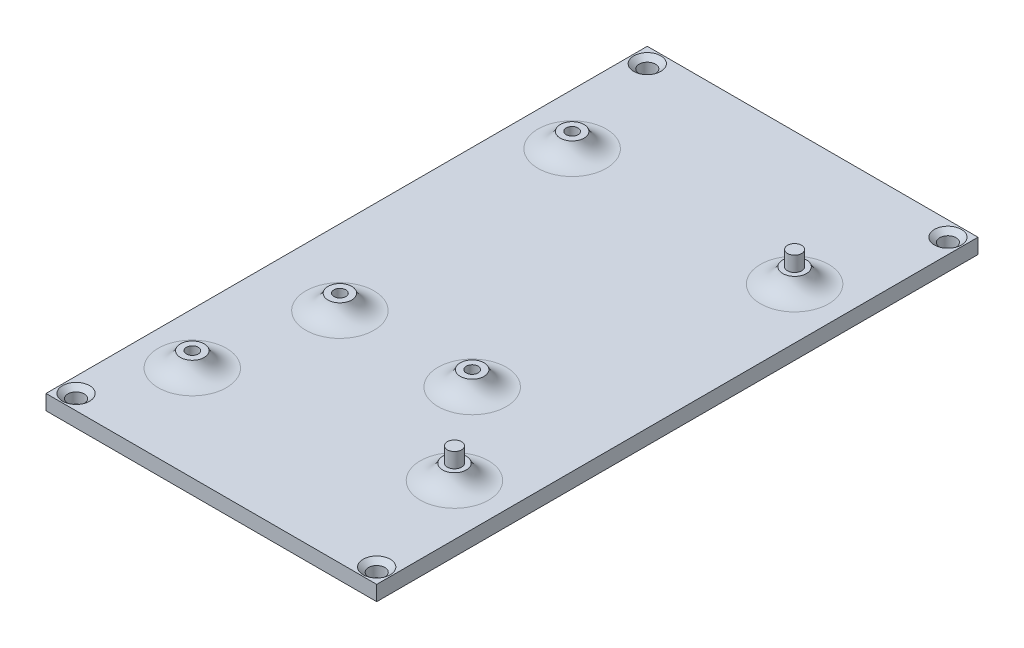
SolidWorks part; units mm, degrees
ref_plane "Front Plane" through (0, 0, 0) normal (0, 0, 1) x (1, 0, 0)
ref_plane "Top Plane" through (0, 0, 0) normal (0, 1, 0) x (1, 0, 0)
ref_plane "Right Plane" through (0, 0, 0) normal (1, 0, 0) x (0, 0, -1)
sketch "Sketch1" plane through (0, 0, 0) normal (0, 1, 0) x (1, 0, 0)
  line L1 (0, 0) -> (69.85, 0)
  line L2 (0, 0) -> (0, 127)
  line L3 (0, 127) -> (69.85, 127)
  line L4 (69.85, 0) -> (69.85, 127)
  dimension "D1" = 127
  dimension "D2" = 69.85
extrude "Boss-Extrude1" add sketch "Sketch1" along normal blind 3.175
sketch "Sketch2" plane through (0, 3.175, 0) normal (0, 1, 0) x (1, 0, 0)
  line L0 (69.85, 0) -> (69.85, 127) construction
  line L1 (8.255, 114.3) -> (61.595, 114.3) construction
  line L2 (8.255, 114.3) -> (8.255, 12.7) construction
  line L3 (8.255, 12.7) -> (61.595, 12.7) construction
  line L4 (61.595, 114.3) -> (61.595, 12.7) construction
  line L5 (0, 0) -> (69.85, 0) construction
  circle A0 centre (10.795, 100.33) radius 2.5
  circle A1 centre (59.055, 99.06) radius 2.5
  circle A2 centre (15.875, 46.1986) radius 2.5
  circle A3 centre (43.815, 46.1986) radius 2.5
  circle A4 centre (10.795, 20.1029) radius 2.5
  circle A5 centre (59.055, 27.217) radius 2.5
  point P20 (0, 0)
  point P21 (0, 0)
  dimension "D5" = 5
  dimension "D1" = 101.6
  dimension "D2" = 53.34
  dimension "D3" = 8.255
  dimension "D4" = 12.7
  dimension "D6" = 1.27
  dimension "D7" = 2.54
  dimension "D8" = 13.97
  dimension "D9" = 2.54
  dimension "D10" = 0
  dimension "D11" = 15.24
  dimension "D12" = 27.94
  dimension "D13" = 5.08
extrude "Boss-Extrude2" add sketch "Sketch2" along normal blind 3.175
hole_wizard "M3x0.5 Tapped Hole1" positions "Sketch3" profile "Sketch4" tap size "M3x0.5" standard "ANSI Metric" end condition through all
sketch "Sketch3" plane through (0, 6.35, 0) normal (0, 1, 0) x (1, 0, 0)
  point P0 (10.795, 100.33)
  point P3 (15.875, 46.1986)
  point P6 (43.815, 46.1986)
  point P9 (10.795, 20.1029)
sketch "Sketch4" plane through (10.795, 6.35, -100.33) normal (1, 0, 0) x (0, 0, 1)
  line L0 (0, 0) -> (0, 6.35)
  line L1 (0, 6.35) -> (1.25, 6.35)
  line L2 (1.25, 6.35) -> (1.25, 0)
  line L5 (1.25, 0) -> (0, 0)
  line L11 (0, -6.35) -> (0, 107.95) construction
  dimension "Thru Tap Drill Dia." = 2.5
  dimension "Thru Tap Drill Depth" = 6.35
cosmetic thread "Hole Thread1" parameters "D2"=3
cosmetic thread "Hole Thread2" parameters "D2"=3
cosmetic thread "Hole Thread3" parameters "D2"=3
cosmetic thread "Hole Thread4" parameters "D2"=3
sketch "Sketch5" plane through (0, 6.35, 0) normal (0, 1, 0) x (1, 0, 0)
  circle A0 centre (59.055, 99.06) radius 1.5
  circle A1 centre (59.055, 27.217) radius 1.5
  dimension "D1" = 3
  dimension "D2" = 3
extrude "Boss-Extrude3" add sketch "Sketch5" along normal blind 3.175
hole_wizard "CSK for #4 Flat Head Machine Screw (100)1" positions "Sketch6" profile "Sketch7" countersink size "#4" standard "ANSI Inch" end condition through all
sketch "Sketch6" plane through (0, 3.175, 0) normal (0, 1, 0) x (1, 0, 0)
  line L0 (69.85, 127) -> (0, 127) construction
  line L1 (0, 127) -> (0, 0) construction
  line L2 (69.85, 0) -> (69.85, 127) construction
  line L3 (0, 0) -> (69.85, 0) construction
  point P0 (3.175, 123.825)
  point P2 (66.675, 123.825)
  point P4 (66.675, 3.175)
  point P6 (3.175, 3.175)
  point P17 (36.612, 152.3647)
  dimension "D1" = 3.175
  dimension "D2" = 3.175
  dimension "D3" = 3.175
  dimension "D4" = 3.175
  dimension "D5" = 3.175
  dimension "D6" = 3.175
  dimension "D7" = 3.175
  dimension "D8" = 3.175
sketch "Sketch7" plane through (3.175, 3.175, -123.825) normal (1, 0, 0) x (0, 0, 1)
  line L0 (0, 0) -> (0, 3.175)
  line L1 (0, 3.175) -> (1.7272, 3.175)
  line L2 (1.7272, 3.175) -> (1.7272, 0.9484)
  line L3 (1.7272, 0.9484) -> (2.8575, 0)
  line L5 (2.8575, 0) -> (0, 0)
  line L6 (-1.7272, 0.9484) -> (-2.8575, 0) construction
  line L11 (0, -6.35) -> (0, 107.95) construction
  dimension "Thru Hole Dia." = 3.4544
  dimension "Thru Hole Depth" = 3.175
  dimension "Near C'Sink Dia." = 5.715
  dimension "Near C'Sink Angle" = 100
fillet "Fillet1" radius 5.08 6 edges at (59.055, 3.175, -29.717) (43.815, 3.175, -48.6986) (10.795, 3.175, -22.6029) (15.875, 3.175, -48.6986) (59.055, 3.175, -101.56) (10.795, 3.175, -102.83)
